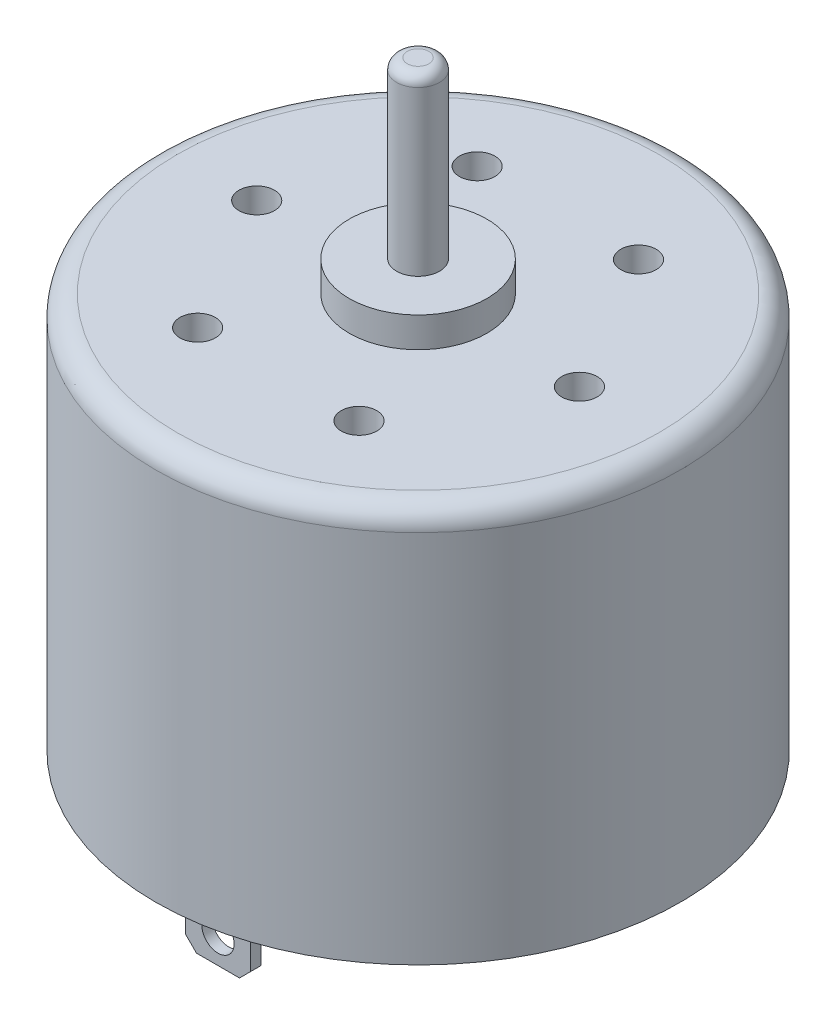
SolidWorks part; units mm, degrees
ref_plane "Front Plane" through (0, 0, 0) normal (0, 0, 1) x (1, 0, 0)
ref_plane "Top Plane" through (0, 0, 0) normal (0, 1, 0) x (1, 0, 0)
ref_plane "Right Plane" through (0, 0, 0) normal (1, 0, 0) x (0, 0, -1)
sketch "Sketch1" plane through (0, 0, 0) normal (0, 1, 0) x (1, 0, 0)
  circle A0 centre (0, 0) radius 12.2
  dimension "D1" = 24.4
extrude "Boss-Extrude1" add sketch "Sketch1" along normal blind 18.4
fillet "Fillet1" radius 1 1 edges at (0, 18.4, 12.2)
hole_wizard "M2x0.35 Tapped Hole1" positions "Sketch3" profile "Sketch4" tap size "M2x0.35" standard "DIN"
sketch "Sketch3" plane through (0, 18.4, 0) normal (0, 1, 0) x (1, 0, 0)
  circle A0 centre (0, 0) radius 7.5 construction
  point P0 (-7.5, 0)
  point P13 (-3.75, 6.4952)
  point P14 (3.75, 6.4952)
  point P15 (7.5, 0)
  point P16 (3.75, -6.4952)
  point P17 (-3.75, -6.4952)
  point P19 (0, 0)
  point P20 (0, 0)
  point P22 (0, 0)
  point P23 (-3.0449, 4.9317)
  point P24 (-2.653, 6.0422)
  point P25 (-2.6114, 7.0307)
  point P26 (7.5, 0)
  dimension "D1" = 15
  dimension "D2" = 6
sketch "Sketch4" plane through (-7.5, 18.4, 0) normal (1, 0, 0) x (0, 0, 1)
  line L0 (0, 0) -> (0, 3.5457)
  line L1 (0, 3.5457) -> (0.825, 3.05)
  line L2 (0.825, 3.05) -> (0.825, 0)
  line L5 (0.825, 0) -> (0, 0)
  line L10 (0, 3.5457) -> (-0.825, 3.05) construction
  line L11 (0, -6.35) -> (0, 107.95) construction
  dimension "Tap Drill Dia." = 1.65
  dimension "Tap Drill Depth" = 3.05
  dimension "Drill Angle" = 118
cosmetic thread "Hole Thread1" parameters "D1"=4, "D2"=2
cosmetic thread "Hole Thread2" parameters "D1"=4, "D2"=2
cosmetic thread "Hole Thread3" parameters "D1"=4, "D2"=2
cosmetic thread "Hole Thread4" parameters "D1"=4, "D2"=2
cosmetic thread "Hole Thread5" parameters "D1"=4, "D2"=2
cosmetic thread "Hole Thread6" parameters "D1"=4, "D2"=2
sketch "Sketch5" plane through (0, 18.4, 0) normal (0, 1, 0) x (1, 0, 0)
  circle A0 centre (0, 0) radius 3.2
  dimension "D1" = 6.4
extrude "Boss-Extrude2" add sketch "Sketch5" along normal blind 1.4
sketch "Sketch6" plane through (0, 19.8, 0) normal (0, 1, 0) x (1, 0, 0)
  circle A0 centre (0, 0) radius 1
  dimension "D1" = 2
extrude "Boss-Extrude3" add sketch "Sketch6" along normal blind 8.1
fillet "Fillet2" radius 0.5 1 edges at (0, 27.9, 1)
sketch "Sketch8" plane through (0, 0, 0) normal (0, -1, 0) x (1, 0, 0)
  circle A0 centre (0, 0) radius 11.9
  dimension "D1" = 23.8
extrude "Cut-Extrude1" cut sketch "Sketch8" against normal blind 0.6
sketch "Sketch9" plane through (0, 0.6, 0) normal (0, -1, 0) x (1, 0, 0)
  circle A0 centre (0, 0) radius 3.225
  dimension "D1" = 6.45
extrude "Boss-Extrude4" add sketch "Sketch9" along normal blind 1.7
fillet "Fillet3" radius 0.5 1 edges at (0, -1.1, -3.225)
sketch "Sketch11" plane through (0, 0.6, 0) normal (0, -1, 0) x (1, 0, 0)
  line L0 (-1.95, 9.05) -> (1.95, 9.05) construction
  line L1 (-1.95, 10.3) -> (1.95, 10.3)
  line L2 (-1.95, 7.8) -> (1.95, 7.8)
  line L3 (-11.9, 0) -> (11.9, 0) construction
  line L4 (-1.95, -9.05) -> (1.95, -9.05) construction
  line L5 (-1.95, -10.3) -> (1.95, -10.3)
  line L6 (-1.95, -7.8) -> (1.95, -7.8)
  arc A0 (-1.95, 10.3) -> (-1.95, 7.8) centre (-1.95, 9.05) ccw
  arc A1 (1.95, 7.8) -> (1.95, 10.3) centre (1.95, 9.05) ccw
  circle A2 centre (0, 0) radius 11.9 construction
  circle A3 centre (0, 0) radius 11.9 construction
  arc A4 (-1.95, -10.3) -> (-1.95, -7.8) centre (-1.95, -9.05) cw
  arc A5 (1.95, -7.8) -> (1.95, -10.3) centre (1.95, -9.05) cw
  point P2 (0, 9.05)
  point P16 (0, -9.05)
  point P21 (0, 0)
  dimension "D3" = 1.25
  dimension "D1" = 18.1
  dimension "D2" = 3.9
extrude "Boss-Extrude5" add sketch "Sketch11" along normal blind 0.5
fillet "Fillet4" radius 0.5 8 edges at (0, 0.1, -7.8) (3.2, 0.1, -9.05) (0, 0.1, -10.3) (-3.2, 0.1, -9.05) (0, 0.1, 10.3) (3.2, 0.1, 9.05) (0, 0.1, 7.8) (-3.2, 0.1, 9.05)
ref_plane "Plane1" through (0, 0, 9.05) normal (0, 0, -1) x (-1, 0, 0)
sketch "Sketch12" plane through (0, 0, 9.05) normal (0, 0, -1) x (-1, 0, 0)
  line L0 (-1.5, 0.1) -> (-1.5, -3.5)
  line L1 (-1.5, -3.5) -> (-1, -4)
  line L2 (-1, -4) -> (1, -4)
  line L3 (1, -4) -> (1.5, -3.5)
  line L4 (1.5, -3.5) -> (1.5, 0.1)
  line L5 (1.5, 0.1) -> (-1.5, 0.1)
  line L6 (-1.5, -3.5) -> (1.5, -3.5) construction
  line L7 (0, 0) -> (0, -4) construction
  circle A0 centre (0, -2.75) radius 0.75
  point P2 (0, 0.1)
  point P7 (0, -4)
  dimension "D5" = 1.5
  dimension "D1" = 45
  dimension "D2" = 4.1
  dimension "D3" = 0.5
  dimension "D4" = 3
  dimension "D6" = 0.1
extrude "Boss-Extrude6" add sketch "Sketch12" along normal mid plane 0.5
mirror "Mirror4" about plane through (0, 0, 0) normal (0, 0, 1) of "Boss-Extrude6"
